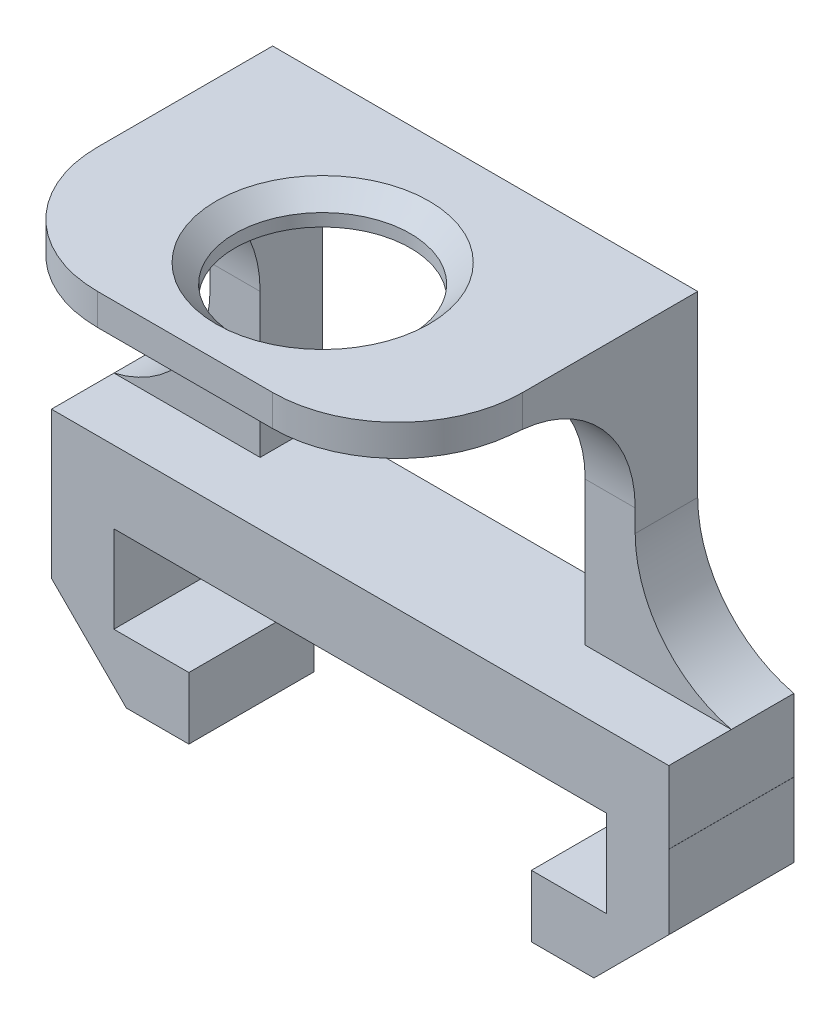
SolidWorks part; units mm, degrees
ref_plane "Front Plane" through (0, 0, 0) normal (0, 0, 1) x (1, 0, 0)
ref_plane "Top Plane" through (0, 0, 0) normal (0, 1, 0) x (1, 0, 0)
ref_plane "Right Plane" through (0, 0, 0) normal (1, 0, 0) x (0, 0, -1)
sketch "Sketch2" plane through (0, 0, 0) normal (0, 0, 1) x (1, 0, 0)
  line L0 (12.3453, 19.45) -> (-12.3453, 19.45)
  line L1 (12.3453, 22.3446) -> (-12.3453, 22.3446)
  line L2 (12.3453, 19.45) -> (12.3453, 22.3446)
  line L8 (-12.3453, 19.45) -> (-12.3453, 22.3446)
  dimension "D2" = 2.8946
extrude "Boss-Extrude2" add sketch "Sketch2" along normal blind 3
extrude "Boss-Extrude3" add sketch "Sketch2<2>" against normal blind 2
sketch "Sketch2<2>" plane through (0, 0, 0) normal (0, 0, 1) x (1, 0, 0) same geometry as "Sketch2"
ref_plane "Plane4" through (0, 0, 3) normal (0, 0, 1) x (1, 0, 0)
ref_plane "Plane6" through (0, 19.45, 0) normal (0, -1, 0) x (-1, 0, 0)
sketch "Sketch8" plane through (0, 19.45, 0) normal (0, -1, 0) x (-1, 0, 0)
  line L1 (-1.592, -3) -> (1.592, -3) construction
  line L2 (12.35, 2) -> (9.85, 2)
  line L3 (12.3453, 2) -> (-12.3453, 2) construction
  line L4 (-9.85, 2) -> (-9.85, -3)
  line L5 (-9.85, -3) -> (-12.35, -3)
  line L6 (-12.35, -3) -> (-12.35, 2)
  line L7 (-12.35, 2) -> (-9.85, 2)
  line L8 (12.35, -3) -> (12.35, 2)
  line L9 (9.85, -3) -> (12.35, -3)
  line L10 (9.85, 2) -> (9.85, -3)
  point P0 (0, 0)
  dimension "D1" = 9.85
  dimension "D2" = 9.85
  dimension "D3" = 2.5
  dimension "D4" = 2.5
  dimension "D5" = 0
extrude "Boss-Extrude4" add sketch "Sketch8" along normal blind 5.96
ref_plane "Plane7" through (9.85, 0, 0) normal (-1, 0, 0) x (0, 0, 1)
sketch "Sketch10" plane through (9.85, 0, 0) normal (-1, 0, 0) x (0, 0, 1)
  line L0 (3, 13.49) -> (-2, 13.49) construction
  line L1 (3, 13.49) -> (-2, 13.49)
  line L2 (3, 13.49) -> (3, 15.97)
  line L3 (3, 15.97) -> (-2, 15.97)
  line L4 (-2, 13.49) -> (-2, 15.97)
  line L5 (-2, 13.49) -> (-2, 19.45) construction
  line L6 (3, 13.49) -> (3, 19.45) construction
  dimension "D1" = 2.48
  dimension "D2" = 0
extrude "Boss-Extrude5" add sketch "Sketch10" along normal blind 3
ref_plane "Plane8" through (-9.85, 0, 0) normal (1, 0, 0) x (0, 0, -1)
sketch "Sketch11" plane through (-9.85, 0, 0) normal (1, 0, 0) x (0, 0, -1)
  line L0 (2, 13.49) -> (2, 19.45) construction
  line L1 (-3, 13.49) -> (2, 13.49)
  line L2 (-3, 13.49) -> (-3, 15.97)
  line L3 (-3, 15.97) -> (2, 15.97)
  line L4 (2, 13.49) -> (2, 15.97)
  dimension "D1" = 2.48
extrude "Boss-Extrude6" add sketch "Sketch11" along normal blind 3
ref_plane "Plane9" through (0, 22.3446, 0) normal (0, 1, 0) x (1, 0, 0)
sketch "Sketch12" plane through (0, 22.3446, 0) normal (0, 1, 0) x (1, 0, 0)
  line L2 (12.3453, 2) -> (-12.3453, 2) construction
  line L5 (8.5, -0.5) -> (8.5, 2)
  line L6 (8.5, 2) -> (-8.5, 2)
  line L7 (-8.5, -0.5) -> (-8.5, 2)
  line L9 (8.5, -0.5) -> (-8.5, -0.5)
  point P6 (0, 0)
  dimension "D1" = 0
  dimension "D2" = 8.5
  dimension "D3" = 2.5
extrude "Boss-Extrude7" add sketch "Sketch12" along normal blind 12
ref_plane "Plane10" through (0, 0, 0.5) normal (0, 0, 1) x (1, 0, 0)
sketch "Sketch14" plane through (0, 0, 0.5) normal (0, 0, 1) x (1, 0, 0)
  line L1 (-8.5, 34.3446) -> (8.5, 34.3446) construction
  line L2 (12.3453, 22.3446) -> (-12.3453, 22.3446) construction
  line L7 (-6.5, 33.0946) -> (6.5, 33.0946)
  line L8 (-6.5, 33.0946) -> (-6.5, 22.3446)
  line L9 (-6.5, 22.3446) -> (6.5, 22.3446)
  line L10 (6.5, 33.0946) -> (6.5, 22.3446)
  dimension "D1" = 1.25
  dimension "D2" = 0
extrude "Cut-Extrude7" cut sketch "Sketch14" against normal up to next
sketch "Sketch16" plane through (0, 0, 0.5) normal (0, 0, 1) x (1, 0, 0)
  line L1 (-8.5, 34.3446) -> (8.5, 34.3446)
  line L2 (-8.5, 34.3446) -> (-8.5, 33.0946)
  line L3 (-8.5, 33.0946) -> (8.5, 33.0946)
  line L4 (8.5, 34.3446) -> (8.5, 33.0946)
  line L5 (-8.5, 34.3446) -> (8.5, 34.3446) construction
  dimension "D1" = 1.25
  dimension "D2" = 0
extrude "Boss-Extrude8" add sketch "Sketch16" along normal blind 9.5
ref_plane "Plane11" through (0, 34.3446, 0) normal (0, 1, 0) x (1, 0, 0)
sketch "Sketch17" plane through (0, 34.3446, 0) normal (0, 1, 0) x (1, 0, 0)
  line L0 (8.5, -10) -> (-8.5, -10) construction
  line L1 (-8.5, 2) -> (-8.5, -10) construction
  circle A0 centre (0, -4.5) radius 3.51
  dimension "D1" = 5.5
  dimension "D2" = 8.5
extrude "Cut-Extrude8" cut sketch "Sketch17" against normal up to next
chamfer "Chamfer1" distance 3 angle 45 1 edges at (-12.35, 13.49, 0.5)
chamfer "Chamfer2" distance 3 angle 45 1 edges at (12.35, 13.49, 0.5)
ref_plane "Plane14" through (-8.5, 0, 0) normal (-1, 0, 0) x (0, 0, 1)
chamfer "Lens Chamfer" distance 0.75 angle 45 1 edges at (0, 34.3446, 8.01)
fillet "Fillet13" radius 5 2 edges at (-7.5, 33.0946, 0.5) (7.5, 33.0946, 0.5)
fillet "Fillet14" radius 5 2 edges
fillet "Fillet15" radius 5 2 edges at (-8.5, 33.7196, 10) (8.5, 33.7196, 10)
chamfer "Chamfer3" distance 0.8 angle 45 5 edges at (8.35, 15.97, -2) (-8.35, 15.97, -2) (-9.85, 17.71, -2)
